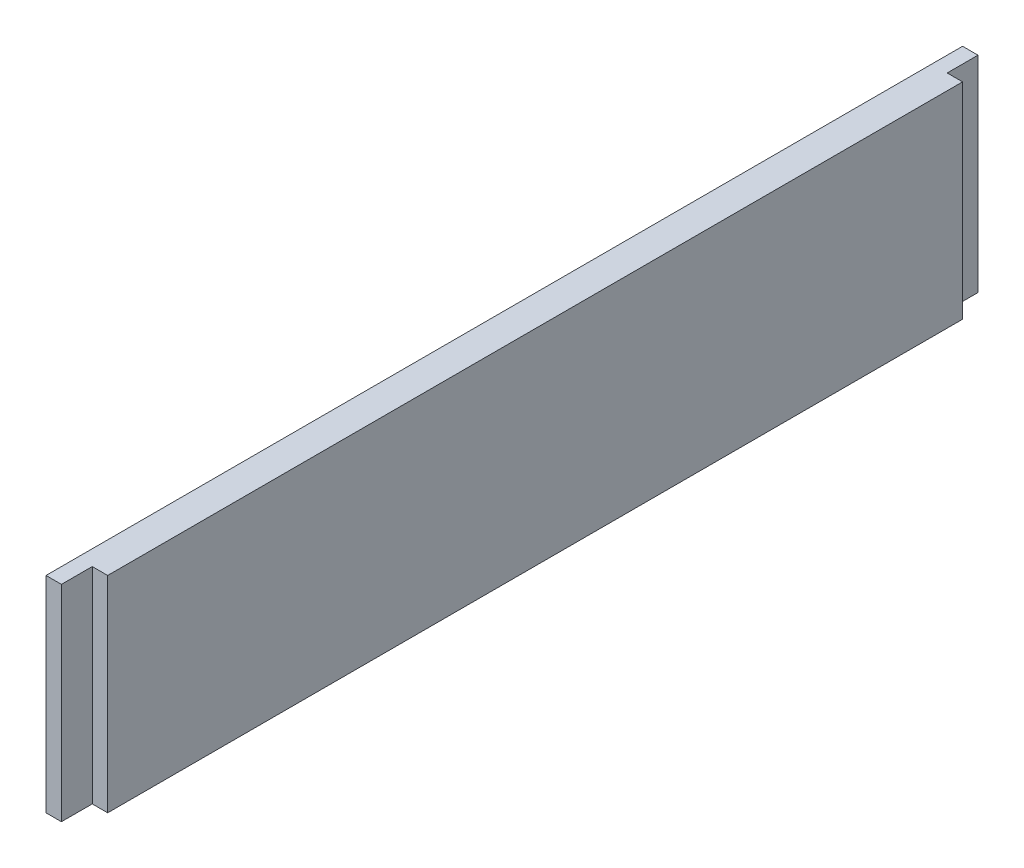
SolidWorks part; units mm, degrees
ref_plane "Front Plane" through (0, 0, 0) normal (0, 0, 1) x (1, 0, 0)
ref_plane "Top Plane" through (0, 0, 0) normal (0, 1, 0) x (1, 0, 0)
ref_plane "Right Plane" through (0, 0, 0) normal (1, 0, 0) x (0, 0, -1)
sketch "Sketch1" plane through (0, 0, 0) normal (1, 0, 0) x (0, 0, -1)
  line L1 (0, 0) -> (535, 0)
  line L2 (0, 0) -> (0, 120)
  line L3 (0, 120) -> (535, 120)
  line L4 (535, 0) -> (535, 120)
  dimension "D1" = 535
  dimension "D2" = 120
extrude "Boss-Extrude1" add sketch "Sketch1" along normal blind 18
sketch "Sketch2" plane through (18, 0, 0) normal (1, 0, 0) x (0, 0, -1)
  line L0 (0, 0) -> (535, 0) construction
  line L1 (0, 120) -> (18, 120)
  line L2 (0, 120) -> (0, 0)
  line L3 (0, 0) -> (18, 0)
  line L4 (18, 120) -> (18, 0)
  line L5 (267.5, 120) -> (267.5, 0) construction
  line L6 (535, 120) -> (0, 120) construction
  line L7 (535, 0) -> (517, 0)
  line L8 (517, 120) -> (517, 0)
  line L9 (535, 120) -> (517, 120)
  line L10 (535, 120) -> (535, 0)
  dimension "D1" = 18
extrude "Cut-Extrude1" cut sketch "Sketch2" against normal blind 9 contours L2 L1 L4 L3 | L7 L8 L9 L10
